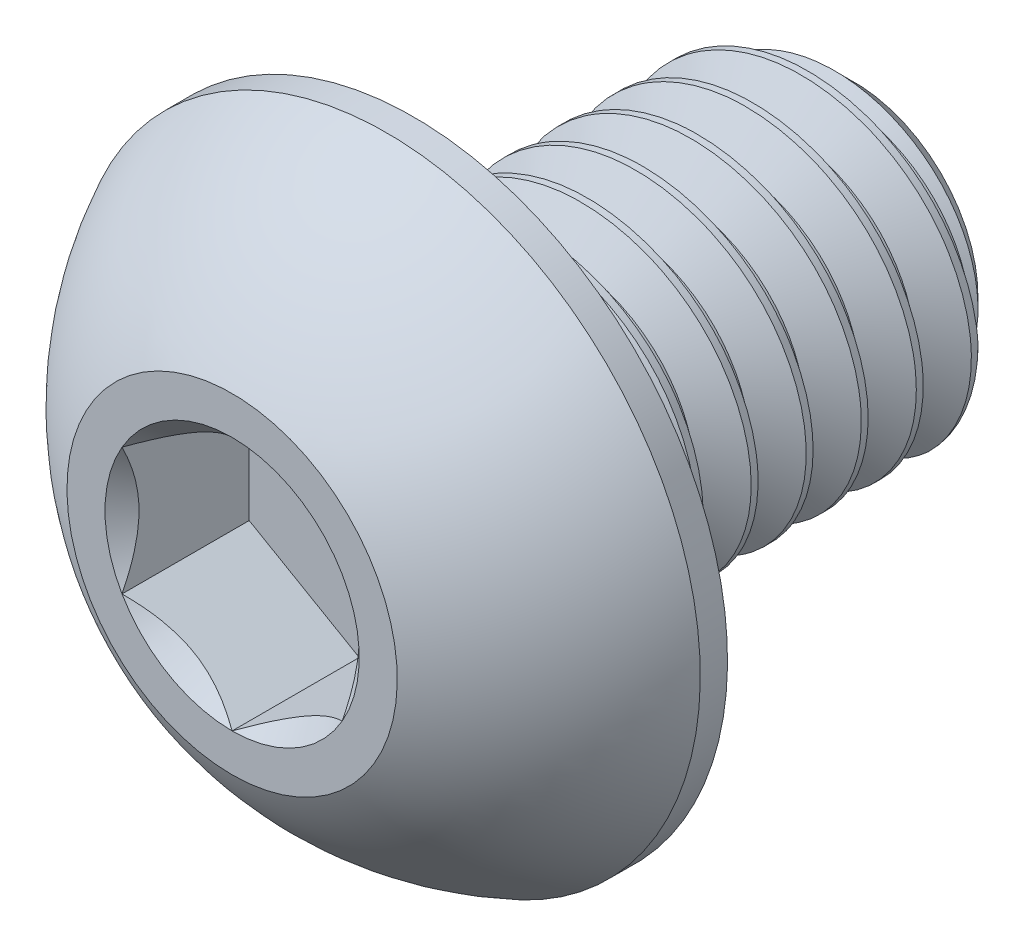
SolidWorks part; units mm, degrees
ref_plane "Front" through (0, 0, 0) normal (0, 0, 1) x (1, 0, 0)
ref_plane "Top" through (0, 0, 0) normal (0, 1, 0) x (1, 0, 0)
ref_plane "Right" through (0, 0, 0) normal (1, 0, 0) x (0, 0, -1)
sketch "Sketch1" plane through (0, 0, 0) normal (1, 0, 0) x (0, 0, -1)
  line L2 (-2, 1.5) -> (2, 1.5)
  line L3 (2, 1.5) -> (2, 0)
  line L4 (2, 0) -> (-2, 0)
  line L6 (-2.2475, 2.85) -> (-2, 2.85) construction
  line L7 (2, 1.5) -> (2, -1.5) construction
  line L8 (-3.65, 0) -> (-2, 0) construction
  line L9 (-2, 2.85) -> (-2, -2.85) construction
  line L11 (-2, 1.5) -> (-2, 0)
  line L13 (-3.65, 1) -> (-3.65, -1) construction
  line L14 (-3.65, 1) -> (-3.65, 1.5) construction
  line L15 (1.9687, 1.5541) -> (2.2188, 1.1211) construction
  line L16 (2.2188, 1.1211) -> (2.4687, 1.5541) construction
  line L17 (2.4687, 1.5541) -> (1.9687, 1.5541) construction
  line L18 (2, 1.5) -> (2.4375, 1.5) construction
  line L19 (2.2188, 1.5541) -> (2.2187, 1.5) construction
  line L20 (2.2187, 1.5) -> (2.2187, 1.1752) construction
  line L21 (2.2187, 1.1752) -> (2.2188, 1.1211) construction
  line L22 (2.1875, 1.1752) -> (2.25, 1.1752)
  line L23 (1.9844, 1.5271) -> (2.4531, 1.5271)
  line L24 (2.25, 1.1752) -> (2.4531, 1.5271)
  line L25 (2.1875, 1.1752) -> (1.9844, 1.5271)
  line L26 (1.625, 1.5) -> (2, 1.125)
  arc A3 (-3.65, 1.5) -> (-2.2475, 2.85) centre (-0.8552, 0) cw construction
  point P29 (2.2187, 1.5271)
  point P30 (0.75, -1.5)
  point P33 (0, 0)
  dimension "Thread Size" = 3
  dimension "D1" = 0.2475
  dimension "Head Height" = 1.65
  dimension "Head Diameter" = 5.7
  dimension "Length" = 4
  dimension "Drive Size" = 2
  dimension "Thread Pitch" = 0.5
  dimension "D3" = 0.0625
  dimension "D2" = 0.375
  dimension "D4" = 45
  dimension "D5" = 1.25
sketch "Sketch10" plane through (0, 0, 0) normal (1, 0, 0) x (0, 0, -1)
  line L0 (1.625, 1.5) -> (2, 1.125) construction
  line L1 (1.625, 1.5) -> (2, 1.125)
  line L4 (2, 1.5) -> (-2, 1.5)
  line L5 (2, 0) -> (2, 1.5)
  line L6 (-2, 0) -> (2, 0)
  line L7 (-2, 1.5) -> (-2, 0)
  line L8 (1.625, 1.5) -> (-2, 1.5)
  line L9 (2, 0) -> (2, 1.125)
  line L10 (-2, 0) -> (2, 0)
  line L11 (-2, 1.5) -> (-2, 0)
  dimension "D1" = 0
revolve "Revolve3" add sketch "Sketch10" angle 360 about L8
sketch "Sketch7" plane through (0, 0, 0) normal (1, 0, 0) x (0, 0, -1)
  line L6 (-2.2475, 2.85) -> (-2, 2.85) construction
  line L8 (-3.65, 0) -> (-2, 0) construction
  line L11 (-2, 2.85) -> (-2, -2.85) construction
  line L12 (-2.2475, 2.85) -> (-2, 2.85)
  line L13 (-3.65, 0) -> (-2, 0)
  line L14 (-3.65, 1) -> (-3.65, -1) construction
  line L15 (-2, 2.85) -> (-2, 0)
  line L16 (-3.65, 1.5) -> (-3.65, 0)
  arc A2 (-2.2475, 2.85) -> (-3.65, 1.5) centre (-0.8552, 0) ccw construction
  arc A3 (-2.2475, 2.85) -> (-3.65, 1.5) centre (-0.8552, 0) ccw
revolve "Revolve2" add sketch "Sketch7" angle 360 mid plane about L13
sketch "Sketch5" plane through (0, 0, 3.65) normal (0, 0, 1) x (1, 0, 0)
  line L1 (1, -0.5774) -> (1, 0.5774)
  line L2 (1, 0.5774) -> (0, 1.1547)
  line L3 (0, 1.1547) -> (-1, 0.5774)
  line L4 (-1, 0.5774) -> (-1, -0.5774)
  line L5 (-1, -0.5774) -> (0, -1.1547)
  line L6 (0, -1.1547) -> (1, -0.5774)
  circle A0 centre (0, 0) radius 1 construction
extrude "Cut-Extrude2" cut sketch "Sketch5" against normal blind 1.155
sketch "Sketch6" plane through (0, 0, 3.65) normal (0, 0, 1) x (1, 0, 0)
  circle A0 centre (0, 0) radius 1.1547
extrude "Cut-Extrude3" cut sketch "Sketch6" against normal blind 1.155 draft 45
sketch "Sketch9" plane through (0, 0, 2) normal (0, 0, -1) x (-1, 0, 0)
  circle A0 centre (0, 0) radius 1.5 construction
  circle A4 centre (0, 0) radius 1.5
split "Split1" bodies to split 113 resulting bodies 123 124 split by face at (0, -2.85, 2)
sketch "Sketch11" plane through (0, 0, -2) normal (0, 0, -1) x (-1, 0, 0)
  circle A0 centre (0, 0) radius 1.5 construction
  circle A1 centre (0, 0) radius 1.5
curve "Helix/Spiral1" pitch 0.5 height 5.65 radius 1.5 centre (0, 0, -2) axis (0, 0, 1) start towards (0, 1, 0)
sketch "Sketch12" plane through (0, 0, 0) normal (1, 0, 0) x (0, 0, -1)
  line L0 (2.1875, 1.1752) -> (2.25, 1.1752) construction
  line L1 (2.25, 1.1752) -> (2.4531, 1.5271) construction
  line L2 (1.9844, 1.5271) -> (2.4531, 1.5271) construction
  line L3 (2.1875, 1.1752) -> (1.9844, 1.5271) construction
  line L4 (2.1875, 1.1752) -> (2.25, 1.1752)
  line L5 (2.25, 1.1752) -> (2.4531, 1.5271)
  line L6 (1.9844, 1.5271) -> (2.4531, 1.5271)
  line L7 (2.1875, 1.1752) -> (1.9844, 1.5271)
sweep "Cut-Sweep2" cut profiles "Sketch12" path "Helix/Spiral1" align with end faces yes
extrude "Boss-Extrude1" add sketch "Sketch9" along normal blind 10 draft 45
equation "\"D1@Cut-Extrude2\" = \"Head Height@Sketch1\" * .7"
equation "\"D1@Sketch1\" = \"Head Height@Sketch1\" * .15"
equation "\"D1@Cut-Extrude3\" = \"D1@Cut-Extrude2\""
equation "\"D3@Sketch1\" = \"Thread Pitch@Sketch1\" / 8"
equation "\"D2@Sketch1\" = \"Thread Pitch@Sketch1\" * 0.75"
equation "\"D3@Helix/Spiral1\" = \"Length@Sketch1\" + \"Head Height@Sketch1\""
equation "\"D4@Helix/Spiral1\" = \"Thread Pitch@Sketch1\""
equation "\"D5@Sketch1\" = \"Thread Pitch@Sketch1\" * 2.5"
